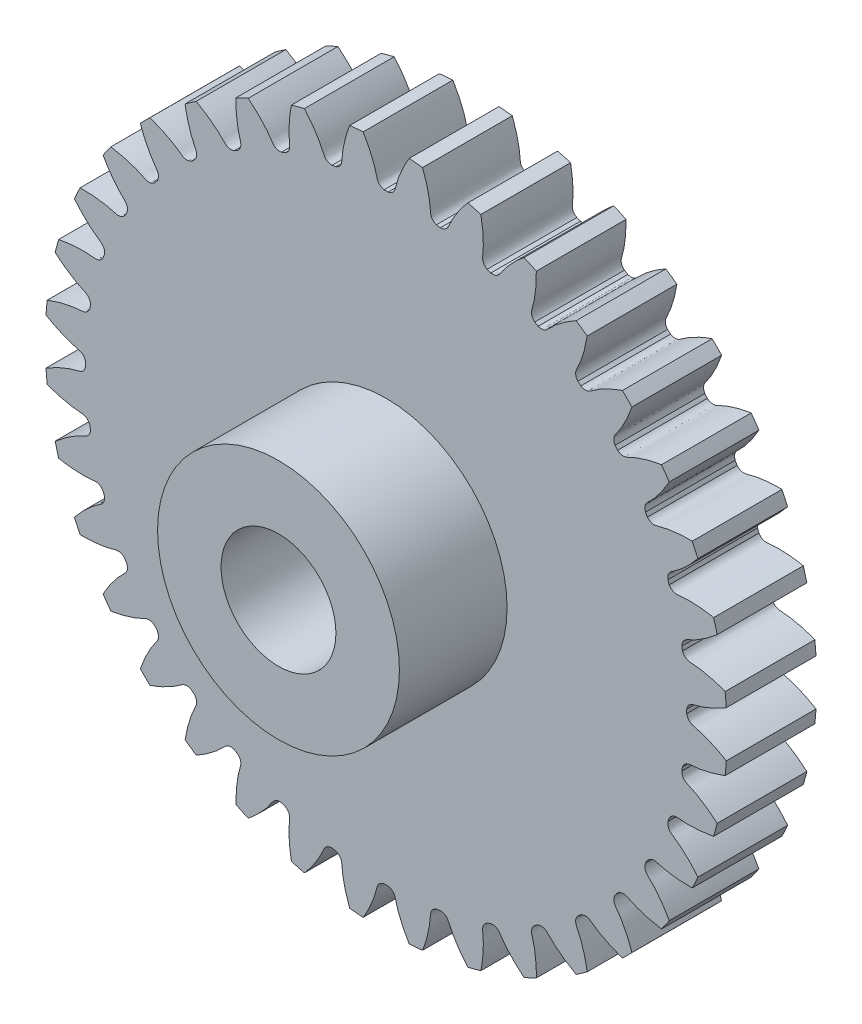
SolidWorks part; units mm, degrees
ref_plane "前视基准面" through (0, 0, 0) normal (0, 0, 1) x (1, 0, 0)
ref_plane "上视基准面" through (0, 0, 0) normal (0, 1, 0) x (1, 0, 0)
ref_plane "右视基准面" through (0, 0, 0) normal (1, 0, 0) x (0, 0, -1)
other "Configuration Table"
sketch "草图1" plane through (0, 0, 0) normal (0, 0, 1) x (1, 0, 0)
  circle A0 centre (0, 0) radius 9.5
extrude "凸台-拉伸1" add sketch "草图1" along normal blind 2.5
ref_axis "基准轴1" through (0, 0, 2.5) along (0, 0, -1)
sketch "草图2" plane through (0, 0, 0) normal (0, 0, 1) x (1, 0, 0)
  line L0 (0, 0) -> (0, 9.5) construction
  circle A0 centre (0, 0) radius 9.5 construction
  arc A1 (0.0549, 8.3748) -> (-0.0549, 8.3748) centre (0, 0) ccw
  arc A2 (1.757, 10.7884) -> (-1.757, 10.7884) centre (0, 0) ccw
  spline S0 degree 3 poles (0.0549, 8.3748) (0.235, 8.4152) (0.2505, 8.5493) (0.2882, 8.6914) (0.2997, 8.7319) (0.3131, 8.7753) (0.3284, 8.8217) (0.3457, 8.871) (0.3652, 8.9231) (0.3869, 8.9779) (0.4111, 9.0354) (0.4378, 9.0956) (0.4671, 9.1582) (0.4992, 9.2232) (0.5341, 9.2907) (0.5719, 9.3603) (0.6128, 9.4322) (0.6569, 9.5061) (0.7043, 9.582) (0.755, 9.6598) (0.8091, 9.7393) (0.8668, 9.8205) (0.9281, 9.9032) (0.9931, 9.9874) (1.0619, 10.0729) (1.1346, 10.1596) (1.2112, 10.2474) (1.2919, 10.3361) (1.3766, 10.4256) (1.4655, 10.5159) (1.5912, 10.6386) (1.6895, 10.7288) (1.757, 10.7884) knots 0 0 0 0 0.120371 0.133303 0.147364 0.162556 0.178878 0.19633 0.214913 0.234626 0.255469 0.277443 0.300547 0.324782 0.350146 0.376641 0.404267 0.433023 0.462909 0.493925 0.526072 0.559349 0.593757 0.629294 0.665963 0.703761 0.74269 0.782749 0.823939 0.866258 0.909709 1 1 1 1
  spline S1 degree 3 poles (-0.0549, 8.3748) (-0.235, 8.4152) (-0.2505, 8.5493) (-0.2882, 8.6914) (-0.2997, 8.7319) (-0.3131, 8.7753) (-0.3284, 8.8217) (-0.3457, 8.871) (-0.3652, 8.9231) (-0.3869, 8.9779) (-0.4111, 9.0354) (-0.4378, 9.0956) (-0.4671, 9.1582) (-0.4992, 9.2232) (-0.5341, 9.2907) (-0.5719, 9.3603) (-0.6128, 9.4322) (-0.6569, 9.5061) (-0.7043, 9.582) (-0.755, 9.6598) (-0.8091, 9.7393) (-0.8668, 9.8205) (-0.9281, 9.9032) (-0.9931, 9.9874) (-1.0619, 10.0729) (-1.1346, 10.1596) (-1.2112, 10.2474) (-1.2919, 10.3361) (-1.3766, 10.4256) (-1.4655, 10.5159) (-1.5912, 10.6386) (-1.6895, 10.7288) (-1.757, 10.7884) knots 0 0 0 0 0.120371 0.133303 0.147364 0.162556 0.178878 0.19633 0.214913 0.234626 0.255469 0.277443 0.300547 0.324782 0.350146 0.376641 0.404267 0.433023 0.462909 0.493925 0.526072 0.559349 0.593757 0.629294 0.665963 0.703761 0.74269 0.782749 0.823939 0.866258 0.909709 1 1 1 1
extrude "切除-拉伸1" cut sketch "草图2" along normal through all
pattern_circular "阵列(圆周)1" count 36 every 10 about axis through (0, 0, 2.5) along (0, 0, -1) of "切除-拉伸1"
sketch "草图3" plane through (0, 0, 0) normal (0, 0, 1) x (1, 0, 0)
  circle A0 centre (0, 0) radius 9 construction
  dimension "Dn" = 18
sketch "草图4" plane through (0, 0, 0) normal (0, 0, -1) x (-1, 0, 0)
  circle A0 centre (0, 0) radius 3.37
  dimension "D1" = 6.74
extrude "凸台-拉伸2" add sketch "草图4" against normal offset from surface (5.5 mm away) 3 up to face at (0, 0, 2.5) offset beyond the face yes
sketch "草图5" plane through (0, 0, 5.5) normal (0, 0, 1) x (1, 0, 0)
  circle A0 centre (0, 0) radius 1.6
  dimension "D1" = 3.2
extrude "切除-拉伸2" cut sketch "草图5" against normal up to next
